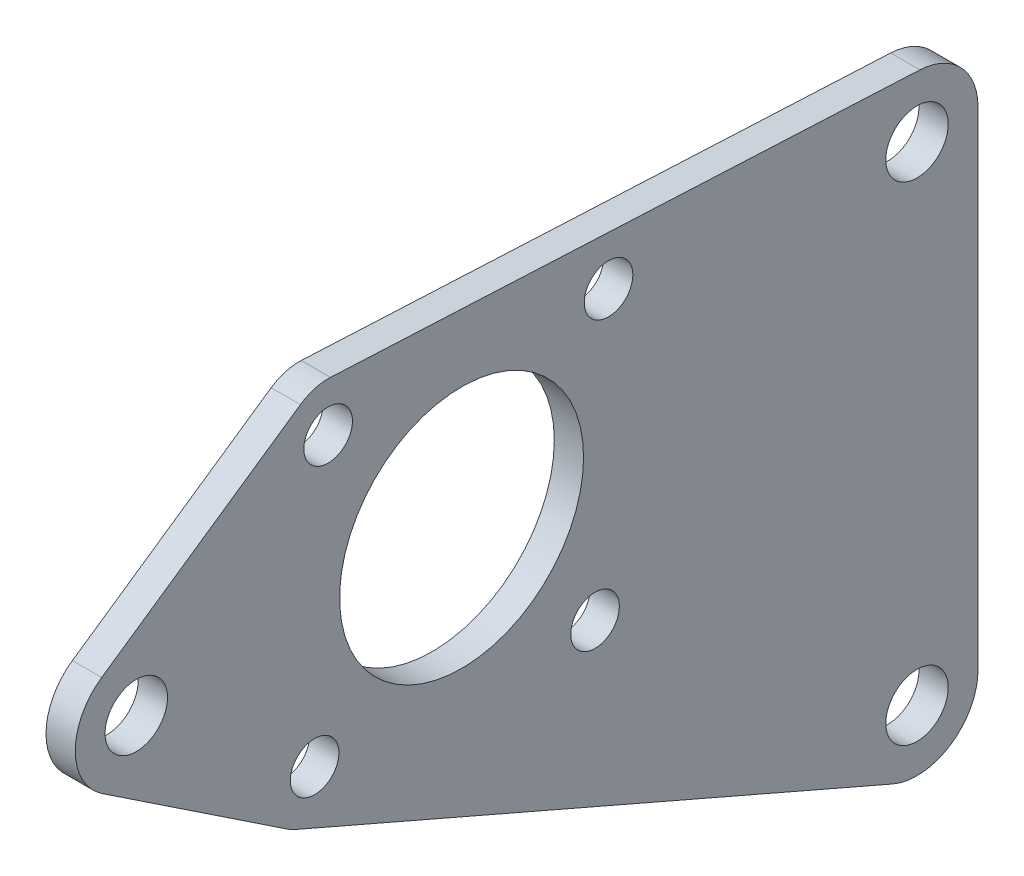
SolidWorks part; units mm, degrees
note: The reader was unsure of these and kept them because the rebuilt part matched: thickness of "Base-Flange1", "Sheet-Metal1", "Sheet-Metal2", "Sheet-Metal7".
material "5052-H32"
ref_plane "Front Plane" through (0, 0, 0) normal (0, 0, 1) x (1, 0, 0)
ref_plane "Top Plane" through (0, 0, 0) normal (0, 1, 0) x (1, 0, 0)
ref_plane "Right Plane" through (0, 0, 0) normal (1, 0, 0) x (0, 0, -1)
sketch "Sketch1" plane through (0, 0, 0) normal (1, 0, 0) x (0, 0, -1)
  line L0 (0, 0) -> (0, 38.1) construction
  line L1 (-60.96, 29.7942) -> (0, 0) construction
  line L2 (-60.96, 29.7942) -> (0, 38.1) construction
  line L4 (4.7625, 38.1) -> (4.7625, 0)
  line L6 (-35.56, 29.7942) -> (-60.96, 29.7942) construction
  line L10 (-25.1401, 18.3193) -> (-45.9799, 41.2691) construction
  line L11 (-24.0851, 40.2141) -> (-47.0349, 19.3743) construction
  line L12 (-45.9799, 41.2691) -> (-24.0851, 40.2141) construction
  line L13 (-63.6616, 33.7163) -> (-48.1412, 44.4068)
  line L14 (-45.7965, 45.0747) -> (0.2292, 42.857)
  line L15 (-63.6002, 25.8305) -> (-49.147, 16.2033)
  line L16 (-48.5517, 15.8792) -> (-1.896, -4.3688)
  line L17 (0, 29.7942) -> (-35.56, 29.7942) construction
  circle A0 centre (0, 38.1) radius 2.4384
  circle A1 centre (0, 0) radius 2.4384
  circle A2 centre (-60.96, 29.7942) radius 2.4384
  circle A3 centre (-60.96, 29.7942) radius 4.7625 construction
  circle A4 centre (0, 0) radius 4.7625 construction
  circle A5 centre (0, 38.1) radius 4.7625 construction
  arc A6 (0.2292, 42.857) -> (4.7625, 38.1) centre (0, 38.1) cw
  arc A7 (4.7625, 0) -> (-1.896, -4.3688) centre (0, 0) cw
  arc A8 (-63.6002, 25.8305) -> (-63.6616, 33.7163) centre (-60.96, 29.7942) cw
  circle A9 centre (-35.56, 29.7942) radius 9.525
  arc A11 (-48.1412, 44.4068) -> (-45.7965, 45.0747) centre (-45.9799, 41.2691) cw
  arc A12 (-49.147, 16.2033) -> (-48.5517, 15.8792) centre (-47.0349, 19.3743) ccw
  dimension "D2" = 4.8768
  dimension "D5" = 9.525
  dimension "D7" = 19.05
  dimension "D8" = 21.9202
  dimension "D9" = 3.81
  dimension "D1" = 38.1
  dimension "D3" = 60.96
  dimension "D4" = 29.7942
  dimension "D6" = 25.4
base flange "Base-Flange1" sketch "Sketch1" thickness 2.286 reverse thickness direction no parameters "D1"=0.7366
hole_wizard "#6 Clearance Hole1" positions "Sketch9" profile "Sketch10" hole size "#6" standard "ANSI Inch" end condition through all
sketch "Sketch9" plane through (0, 0, 0) normal (1, 0, 0) x (0, 0, -1)
  point P0 (-24.0851, 40.2141)
  point P2 (-45.9799, 41.2691)
  point P4 (-25.1401, 18.3193)
  point P20 (-47.0349, 19.3743)
sketch "Sketch10" plane through (0, 40.2141, 24.0851) normal (0, 1, 0) x (0, 0, -1)
  line L0 (0, 0) -> (0, 2.286)
  line L1 (0, 2.286) -> (1.8986, 2.286)
  line L2 (1.8986, 2.286) -> (1.8986, 0)
  line L5 (1.8986, 0) -> (0, 0)
  line L11 (0, -6.35) -> (0, 107.95) construction
  dimension "Thru Hole Dia." = 3.7973
  dimension "Thru Hole Depth" = 2.286
sketch "Sketch11" [suppressed] plane through (0, 0, 0) normal (1, 0, 0) x (0, 0, -1)
  line L5 (0.2292, 42.857) -> (-45.7965, 45.0747) construction
  line L6 (24.5219, 28.9717) -> (11.8366, 29.583)
  line L7 (24.5219, 28.9717) -> (25.1332, 41.657)
  line L8 (25.1332, 41.657) -> (12.4479, 42.2682)
  line L9 (11.8366, 29.583) -> (12.4479, 42.2682)
  line L10 (24.5219, 28.9717) -> (12.4479, 42.2682) construction
  line L11 (25.1332, 41.657) -> (11.8366, 29.583) construction
  point P4 (18.4849, 35.62)
  dimension "D1" = 12.7
extrude "Boss-Extrude1" [suppressed] add sketch "Sketch11" against normal up to surface (2.286 mm away) separate body
sketch "Sketch13" [suppressed] plane through (-2.286, 0, 0) normal (-1, 0, 0) x (0, 0, 1)
  line L0 (-4.7625, 11.7577) -> (-4.7625, 27.0154)
  line L1 (-4.7625, 11.7577) -> (-18.7915, 11.7577)
  line L2 (-4.7625, 27.0154) -> (-18.7915, 27.0154)
  line L3 (-18.7915, 11.7577) -> (-18.7915, 27.0154)
  line L4 (-4.7625, 0) -> (-4.7625, 38.1) construction
  line L5 (26.1996, 44.1304) -> (10.9596, 43.3961)
  line L6 (26.1996, 44.1304) -> (25.5427, 57.7641)
  line L7 (10.9596, 43.3961) -> (10.3027, 57.0298)
  line L8 (25.5427, 57.7641) -> (10.3027, 57.0298)
  line L9 (-0.2292, 42.857) -> (45.7965, 45.0747) construction
  line L10 (34.3268, 9.7058) -> (20.3304, 3.6315)
  line L11 (34.3268, 9.7058) -> (38.7714, -0.5353)
  line L12 (20.3304, 3.6315) -> (24.775, -6.6096)
  line L13 (38.7714, -0.5353) -> (24.775, -6.6096)
  line L14 (48.5517, 15.8792) -> (1.896, -4.3688) construction
  line L15 (61.3163, 35.3317) -> (48.751, 43.9867)
  line L16 (61.3163, 35.3317) -> (65.096, 40.8191)
  line L17 (48.751, 43.9867) -> (52.5307, 49.4742)
  line L18 (65.096, 40.8191) -> (52.5307, 49.4742)
  line L19 (48.1412, 44.4068) -> (63.6616, 33.7163) construction
  dimension "D1" = 15.24
extrude "Boss-Extrude2" [suppressed] add sketch "Sketch13" against normal blind 1.27
sketch "Bend-Lines1" [suppressed] plane through (0, 0, 0) normal (0, 1, 0) x (1, 0, 0)
sketch "Bounding-Box1" [suppressed] plane through (0, 0, 0) normal (0, 1, 0) x (1, 0, 0)
sheet metal parameters "Sheet-Metal1" thickness 2.286 parameters "D1"=0.7366
flat pattern "Flat-Pattern1" [suppressed]
sketch "Bend-Lines2" plane through (0, 0, 0) normal (0, 1, 0) x (1, 0, 0)
sketch3d "Bounding-Box2" [suppressed]
  line L0 (57.8284, -12.9027, 0) -> (-4.7624, -12.9027, 0) construction
  line L1 (57.8284, 34.7222, 0) -> (-4.7624, 34.7222, 0) construction
  line L2 (57.8284, -12.9027, 0) -> (57.8284, 34.7222, 0) construction
  line L3 (-4.7624, -12.9027, 0) -> (-4.7624, 34.7222, 0) construction
sheet metal parameters "Sheet-Metal2" thickness 2.286 parameters "D1"=0.7366, "D7"=1.524
flat pattern "Flat-Pattern1"
sketch "Bend-Lines2" plane through (0, 0, 0) normal (0, 1, 0) x (1, 0, 0)
sketch3d "Bounding-Box2" [suppressed]
  line L0 (65.4878, -34.7803, 0) -> (-6.2772, -31.3225, 0) construction
  line L1 (67.7777, 12.7453, 0) -> (-3.9873, 16.2032, 0) construction
  line L2 (65.4878, -34.7803, 0) -> (67.7777, 12.7453, 0) construction
  line L3 (-6.2772, -31.3225, 0) -> (-3.9873, 16.2032, 0) construction
sheet metal parameters "Sheet-Metal7" [suppressed] thickness 2.286 parameters "D1"=0.7366, "D7"=1.524
flat pattern "Flat-Pattern1"
sketch "Bend-Lines2" plane through (0, 0, 0) normal (0, 1, 0) x (1, 0, 0)
sketch3d "Bounding-Box2" [suppressed]
  line L0 (65.4878, -34.7803, 0) -> (-6.2772, -31.3225, 0) construction
  line L1 (67.7777, 12.7453, 0) -> (-3.9873, 16.2032, 0) construction
  line L2 (65.4878, -34.7803, 0) -> (67.7777, 12.7453, 0) construction
  line L3 (-6.2772, -31.3225, 0) -> (-3.9873, 16.2032, 0) construction
